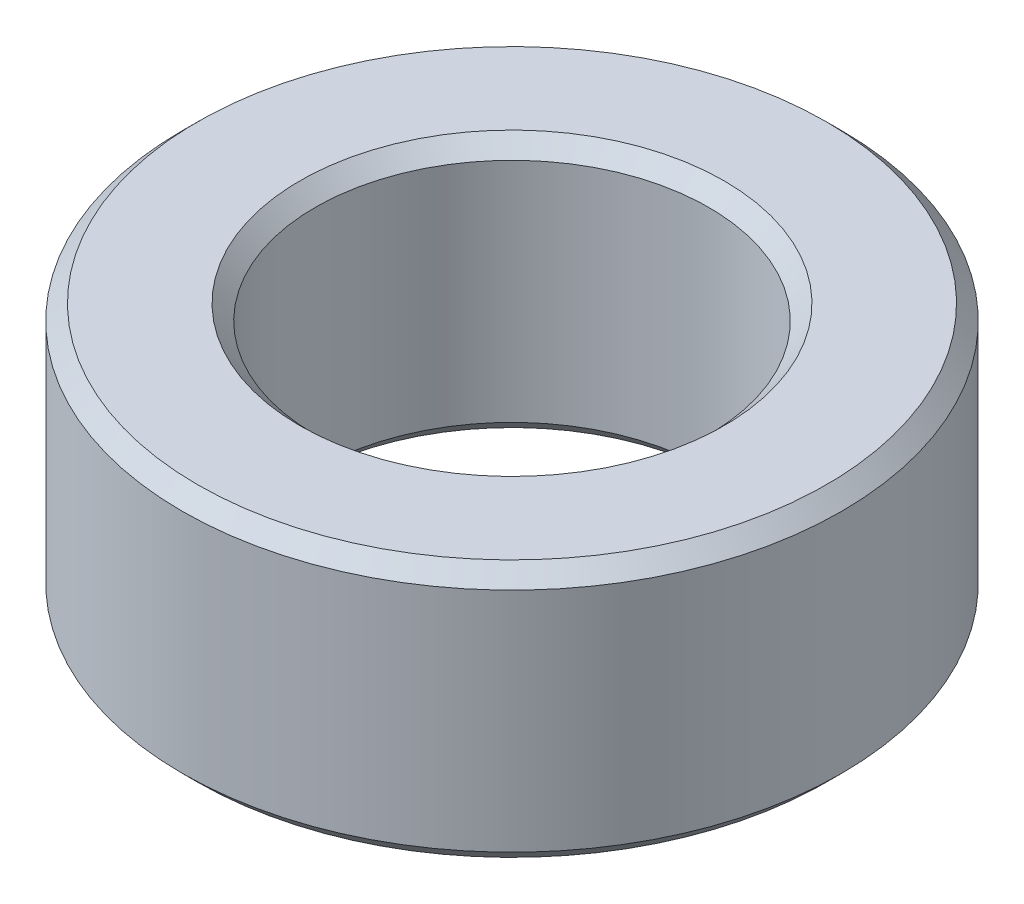
SolidWorks part; units mm, degrees
ref_plane "Front Plane" through (0, 0, 0) normal (0, 0, 1) x (1, 0, 0)
ref_plane "Top Plane" through (0, 0, 0) normal (0, 1, 0) x (1, 0, 0)
ref_plane "Right Plane" through (0, 0, 0) normal (1, 0, 0) x (0, 0, -1)
sketch "Sketch2" plane through (0, 0, 0) normal (1, 0, 0) x (0, 0, -1)
  line L0 (0, 44.5665) -> (0, -36.0862) construction
  line L1 (-32.25, 11.1) -> (-30.75, 12.6)
  line L2 (-30.75, 12.6) -> (-20.75, 12.6)
  line L3 (-32.25, 11.1) -> (-32.25, -11.1)
  line L4 (-30.75, -12.6) -> (-20.75, -12.6)
  line L5 (-19.25, 11.1) -> (-19.25, -11.1)
  line L6 (-32.25, 12.6) -> (-19.25, -12.6) construction
  line L7 (-32.25, -12.6) -> (-19.25, 12.6) construction
  line L8 (-20.75, 12.6) -> (-19.25, 11.1)
  line L9 (-32.25, -11.1) -> (-30.75, -12.6)
  line L10 (-20.75, -12.6) -> (-19.25, -11.1)
  point P3 (-25.75, 0)
  point P8 (0, 0)
  dimension "D1" = 38.5
  dimension "D2" = 64.5
  dimension "D3" = 25.2
revolve "Revolve1" add sketch "Sketch2" angle 360 about L0
